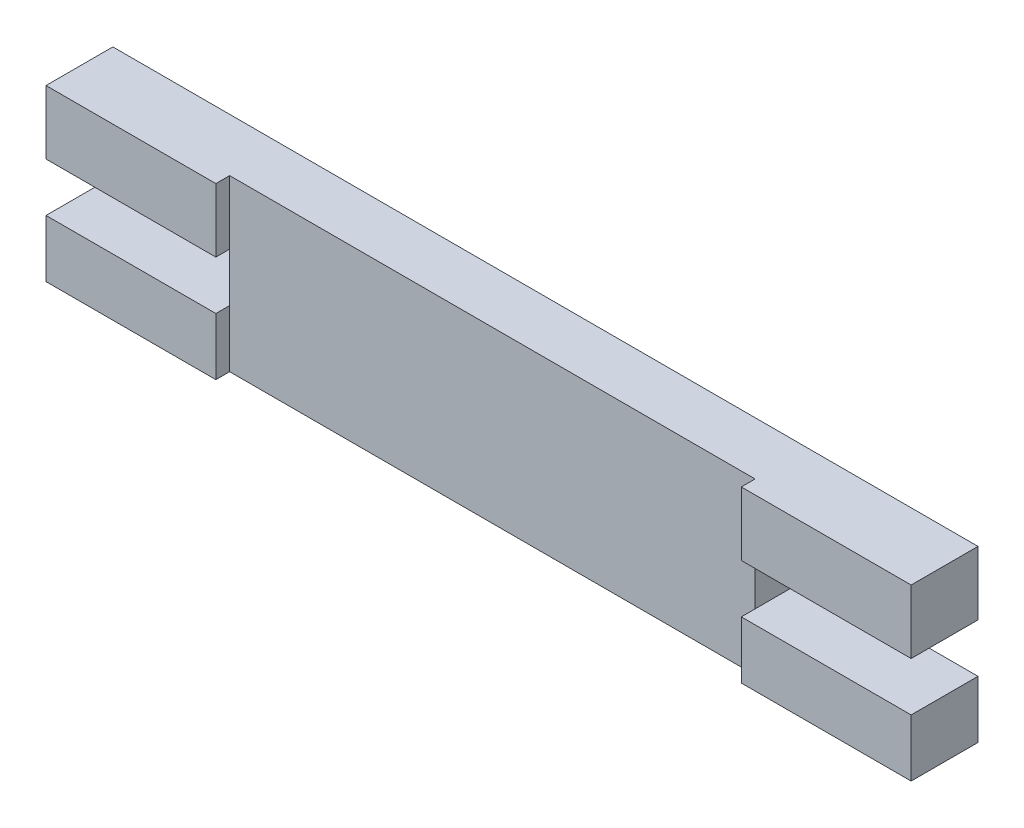
SolidWorks part; units mm, degrees
note: The reader was unsure of these and kept them because the rebuilt part matched: shared geometry of "Sketch1<3>".
ref_plane "Front Plane" through (0, 0, 0) normal (0, 0, 1) x (1, 0, 0)
ref_plane "Top Plane" through (0, 0, 0) normal (0, 1, 0) x (1, 0, 0)
ref_plane "Right Plane" through (0, 0, 0) normal (1, 0, 0) x (0, 0, -1)
sketch "Sketch1" plane through (0, 0, 0) normal (0, 0, 1) x (1, 0, 0)
  line L0 (-16.6216, 4) -> (-16.6216, 1)
  line L1 (-20.375, 4) -> (20.375, 4)
  line L2 (-20.375, 4) -> (-20.375, -4)
  line L3 (-20.375, -4) -> (20.375, -4)
  line L4 (20.375, 4) -> (20.375, -4)
  line L5 (-20.375, 4) -> (20.375, -4) construction
  line L6 (-20.375, -4) -> (20.375, 4) construction
  line L7 (-20.375, 1) -> (-12.375, 1)
  line L8 (-12.375, 1) -> (-12.375, 4)
  line L9 (-16.6216, -4) -> (-16.6216, -1.3)
  line L10 (-20.375, -1.3) -> (-12.375, -1.3)
  line L11 (-12.375, -1.3) -> (-12.375, -4)
  line L12 (-12.375, 1) -> (-12.375, -1.3)
  line L13 (12.375, -1.3) -> (12.375, -4)
  line L14 (20.375, -1.3) -> (12.375, -1.3)
  line L15 (12.375, 1) -> (12.375, 4)
  line L16 (20.375, 1) -> (12.375, 1)
  line L17 (12.375, 1) -> (12.375, -1.3)
  point P0 (0, 0)
  dimension "D1" = 8
  dimension "D2" = 40.75
  dimension "D3" = 3
  dimension "D4" = 8
  dimension "D5" = 2.7
extrude "Boss-Extrude1" add sketch "Sketch1" along normal blind 2.5 contours L4 L16 L15 L1 L8 L7 L2 L10 L11 L3 L13 L14
extrude "Boss-Extrude2" add sketch "Sketch1<3>" along normal blind 3.15 contours L2 L7 L0 L1 | L7 L8 L1 L0 | L11 L10 L9 L3 | L10 L2 L3 L9 | L4 L14 L13 L3 | L16 L4 L1 L15
sketch "Sketch1<3>" plane through (0, 0, 0) normal (0, 0, 1) x (1, 0, 0) same geometry as "Sketch1"
